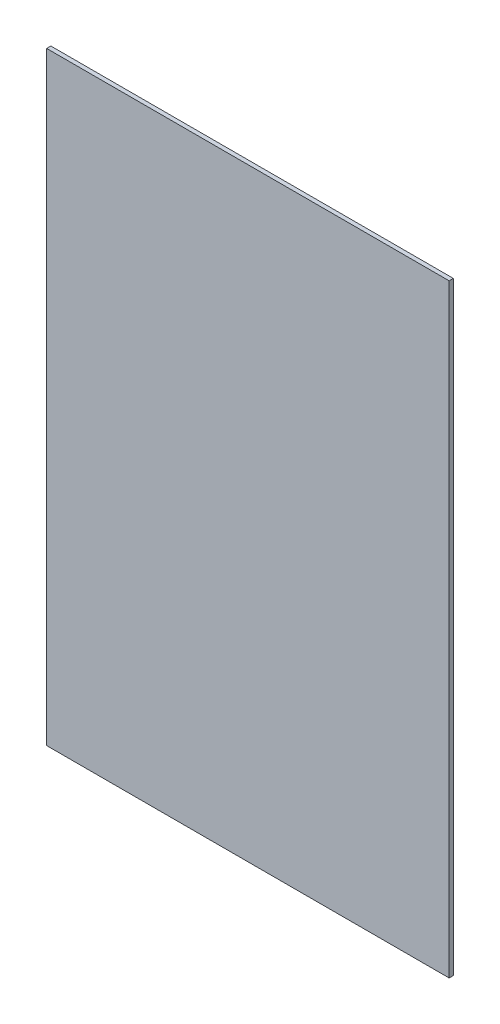
SolidWorks part; units mm, degrees
material "Plain Carbon Steel"
ref_plane "Front Plane" through (0, 0, 0) normal (0, 0, 1) x (1, 0, 0)
ref_plane "Top Plane" through (0, 0, 0) normal (0, 1, 0) x (1, 0, 0)
ref_plane "Right Plane" through (0, 0, 0) normal (1, 0, 0) x (0, 0, -1)
sketch "Sketch1" plane through (0, 0, 0) normal (0, 0, 1) x (1, 0, 0)
  line L1 (-304.8, -457.2) -> (304.8, -457.2)
  line L2 (-304.8, -457.2) -> (-304.8, 457.2)
  line L3 (-304.8, 457.2) -> (304.8, 457.2)
  line L4 (304.8, -457.2) -> (304.8, 457.2)
  line L5 (-304.8, -457.2) -> (304.8, 457.2) construction
  line L6 (-304.8, 457.2) -> (304.8, -457.2) construction
  point P0 (0, 0)
  dimension "D1" = 914.4
  dimension "D2" = 609.6
extrude "Boss-Extrude1" add sketch "Sketch1" along normal mid plane 6.35
